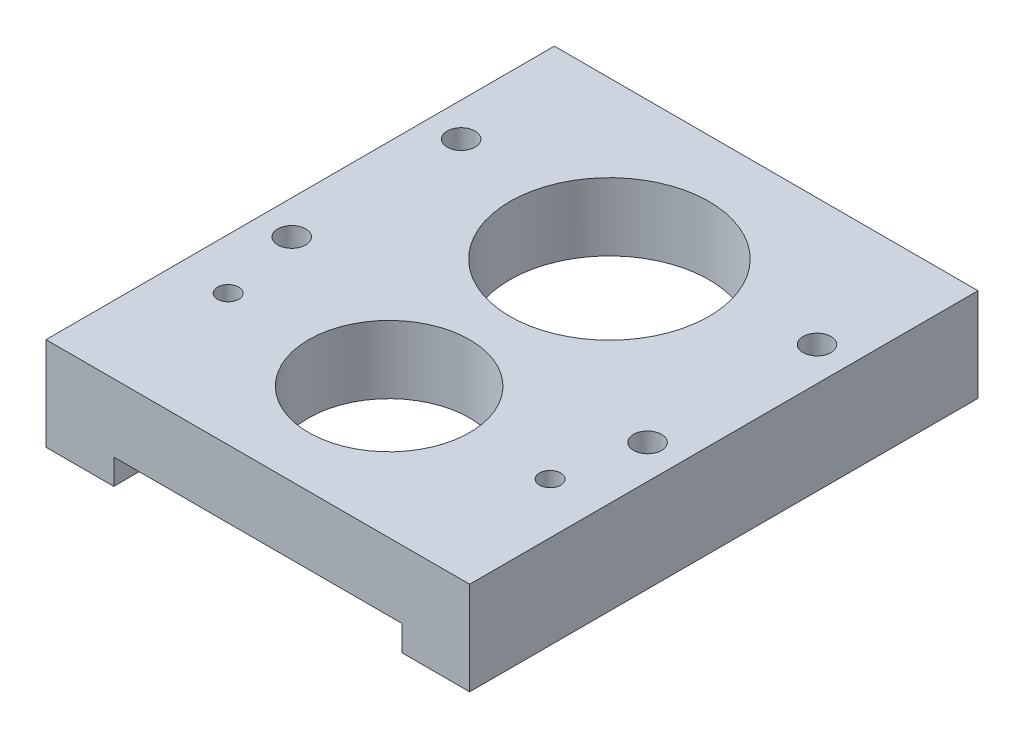
SolidWorks part; units mm, degrees
material "6061 合金"
ref_plane "前基準面" through (0, 0, 0) normal (0, 0, 1) x (1, 0, 0)
ref_plane "上基準面" through (0, 0, 0) normal (0, 1, 0) x (1, 0, 0)
ref_plane "右基準面" through (0, 0, 0) normal (1, 0, 0) x (0, 0, -1)
sketch "草圖1" plane through (0, 0, 0) normal (0, 0, 1) x (1, 0, 0)
  line L0 (-25, 0) -> (-17, 0)
  line L1 (-17, 0) -> (-17, 3)
  line L2 (-17, 3) -> (17, 3)
  line L3 (17, 3) -> (17, 0)
  line L4 (17, 0) -> (25, 0)
  line L5 (25, 0) -> (25, 11)
  line L6 (25, 11) -> (-25, 11)
  line L7 (-25, 11) -> (-25, 0)
  point P3 (0, 3)
  dimension "D1" = 3
  dimension "D2" = 11
  dimension "D3" = 8
  dimension "D4" = 50
extrude "填料-伸長1" add sketch "草圖1" along normal blind 60
sketch "草圖2" plane through (0, 11, 0) normal (0, 1, 0) x (1, 0, 0)
  line L0 (25, 0) -> (-25, 0) construction
  circle A0 centre (0, -18.5) radius 11.75
  point P5 (0, 0)
  dimension "D2" = 23.5
  dimension "D1" = 18.5
extrude "除料-伸長1" cut sketch "草圖2" against normal blind 40
sketch "草圖3" plane through (0, 11, 0) normal (0, 1, 0) x (1, 0, 0)
  line L0 (25, 0) -> (-25, 0) construction
  circle A0 centre (0, -44.5) radius 9.5
  circle A1 centre (0, -18.5) radius 11.75 construction
  point P7 (0, 0)
  dimension "D1" = 26
  dimension "D2" = 19
extrude "除料-伸長2" cut sketch "草圖3" against normal blind 40
hole_wizard "M3x0.5 螺紋孔1" positions "草圖5" profile "草圖6" tap size "M3x0.5" standard "Ansi Metric"
sketch "草圖5" plane through (0, 11, 0) normal (0, 1, 0) x (1, 0, 0)
  line L0 (25, -60) -> (25, 0) construction
  line L1 (25, -60) -> (-25, -60) construction
  line L2 (-25, -60) -> (-25, 0) construction
  point P0 (19, -44.5)
  point P3 (-19, -44.5)
  dimension "D1" = 6
  dimension "D2" = 15.5
  dimension "D3" = 6
  dimension "D4" = 15.5
sketch "草圖6" plane through (19, 11, 44.5) normal (1, 0, 0) x (0, 0, 1)
  line L0 (0, 0) -> (0, 5.7511)
  line L1 (0, 5.7511) -> (1.25, 5)
  line L2 (1.25, 5) -> (1.25, 0)
  line L5 (1.25, 0) -> (0, 0)
  line L10 (0, 5.7511) -> (-1.25, 5) construction
  line L11 (0, -6.35) -> (0, 107.95) construction
  dimension "螺孔鑽直徑" = 2.5
  dimension "螺孔鑽深度" = 5
  dimension "導頭角度" = 118
cosmetic thread "鑽孔螺紋1" parameters "D1"=6, "D2"=3
cosmetic thread "鑽孔螺紋2" parameters "D1"=6, "D2"=3
sketch "草圖7" plane through (0, 11, 0) normal (0, 1, 0) x (1, 0, 0)
  line L0 (25, 0) -> (-25, 0) construction
  line L1 (21, -35) -> (-21, -35) construction
  line L2 (21, -35) -> (21, -15) construction
  line L3 (21, -15) -> (-21, -15) construction
  line L4 (-21, -35) -> (-21, -15) construction
  circle A0 centre (-21, -35) radius 1.65
  circle A1 centre (-21, -15) radius 1.65
  circle A2 centre (21, -35) radius 1.65
  circle A3 centre (21, -15) radius 1.65
  point P8 (0, -35)
  point P11 (0, 0)
  dimension "D1" = 3.3
  dimension "D2" = 3.3
  dimension "D3" = 3.3
  dimension "D4" = 3.3
  dimension "D5" = 20
  dimension "D6" = 42
  dimension "D7" = 15
extrude "除料-伸長3" cut sketch "草圖7" against normal up to next
